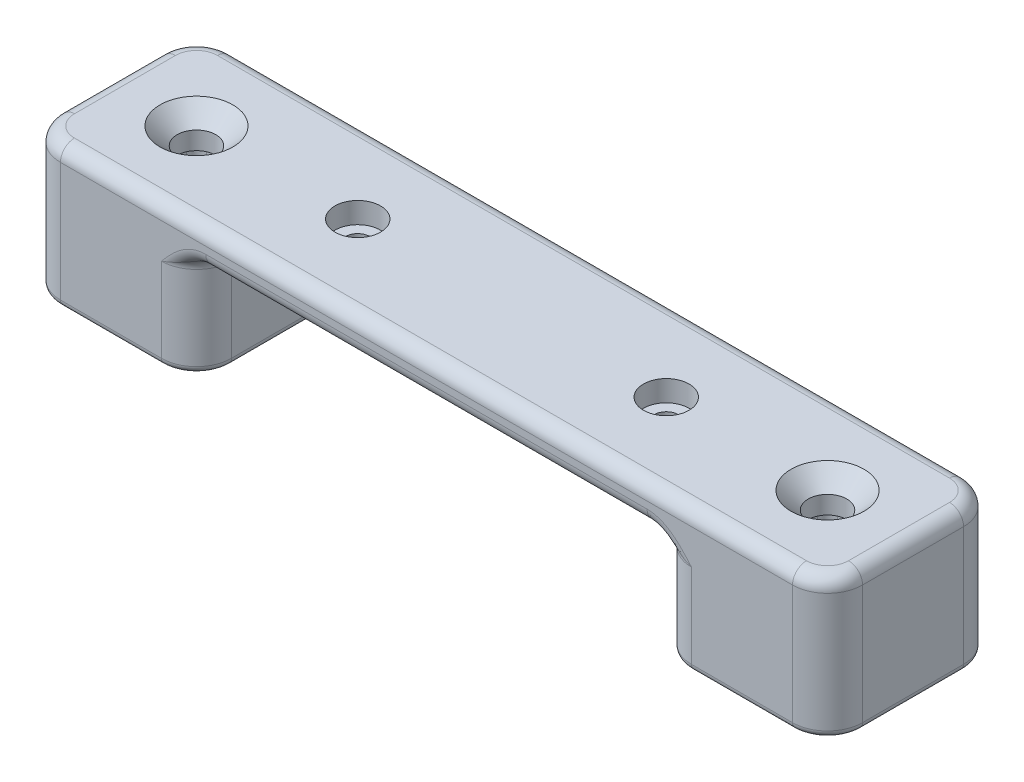
SolidWorks part; units mm, degrees
ref_plane "Plan de face" through (0, 0, 0) normal (0, 0, 1) x (1, 0, 0)
ref_plane "Plan de dessus" through (0, 0, 0) normal (0, 1, 0) x (1, 0, 0)
ref_plane "Plan de droite" through (0, 0, 0) normal (1, 0, 0) x (0, 0, -1)
sketch "Esquisse1" plane through (0, 0, 0) normal (0, 1, 0) x (1, 0, 0)
  line L0 (0, -55) -> (0, 55) construction
  line L1 (-57.2, 12.2) -> (57.2, 12.2)
  line L2 (-57.2, 12.2) -> (-57.2, -12.2)
  line L3 (-57.2, -12.2) -> (57.2, -12.2)
  line L4 (57.2, 12.2) -> (57.2, -12.2)
  line L5 (-55, 0) -> (55, 0) construction
  point P6 (0, -12.2)
  point P11 (57.2, 0)
  dimension "D1" = 114.4
  dimension "D2" = 24.4
extrude "Boss.-Extru.1" add sketch "Esquisse1" along normal blind 5
sketch "Esquisse11" plane through (0, 0, 0) normal (0, -1, 0) x (1, 0, 0)
  line L0 (57.2, -12.2) -> (-57.2, -12.2) construction
  line L1 (-57.2, 12.2) -> (-32.8, 12.2)
  line L2 (-57.2, 12.2) -> (-57.2, -12.2)
  line L3 (-57.2, -12.2) -> (-32.8, -12.2)
  line L4 (-32.8, 12.2) -> (-32.8, -12.2)
  line L10 (57.2, 12.2) -> (32.8, 12.2)
  line L11 (57.2, 12.2) -> (57.2, -12.2)
  line L12 (57.2, -12.2) -> (32.8, -12.2)
  line L13 (32.8, 12.2) -> (32.8, -12.2)
extrude "Boss.-Extru.2" add sketch "Esquisse11" along normal blind 15
sketch "Esquisse12" plane through (0, -15, 0) normal (0, -1, 0) x (1, 0, 0)
  line L8 (-34.8, -10.2) -> (-34.8, 10.2)
  line L9 (-55.2, -10.2) -> (-34.8, -10.2)
  line L10 (-55.2, 10.2) -> (-55.2, -10.2)
  line L11 (-34.8, 10.2) -> (-55.2, 10.2)
  line L12 (-34.8, -10.2) -> (-34.8, 10.2)
  line L13 (-55.2, -10.2) -> (-34.8, -10.2)
  line L14 (-55.2, 10.2) -> (-55.2, -10.2)
  line L15 (-34.8, 10.2) -> (-55.2, 10.2)
  line L20 (55.2, -10.2) -> (55.2, 10.2)
  line L21 (34.8, -10.2) -> (55.2, -10.2)
  line L22 (34.8, 10.2) -> (34.8, -10.2)
  line L23 (55.2, 10.2) -> (34.8, 10.2)
  line L24 (55.2, -10.2) -> (55.2, 10.2)
  line L25 (34.8, -10.2) -> (55.2, -10.2)
  line L26 (34.8, 10.2) -> (34.8, -10.2)
  line L27 (55.2, 10.2) -> (34.8, 10.2)
  dimension "D1" = 2
  dimension "D2" = 2
extrude "Enlèv. mat.-Extru.5" cut sketch "Esquisse12" against normal up to surface (15 mm away) up to face at (0, 0, 0)
sketch "Esquisse20" plane through (0, 5, 0) normal (0, 1, 0) x (1, 0, 0)
  line L0 (-45, 0) -> (45, 0) construction
  point P2 (-45, 0)
  dimension "D1" = 90
hole_wizard "Fraisage pour vis à tête fraisée M51" positions "Esquisse21" profile "Esquisse22" countersink size "M5" standard "ISO" end condition up to next
sketch "Esquisse21" plane through (0, 5, 0) normal (0, 1, 0) x (1, 0, 0)
  point P0 (-45, 0)
  point P3 (45, 0)
sketch "Esquisse22" plane through (-45, 5, 0) normal (1, 0, 0) x (0, 0, 1)
  line L0 (0, 0) -> (0, 5)
  line L1 (0, 5) -> (2.75, 5)
  line L2 (2.75, 5) -> (2.75, 2.45)
  line L3 (2.75, 2.45) -> (5.2, 0)
  line L5 (5.2, 0) -> (0, 0)
  line L6 (-2.75, 2.45) -> (-5.2, 0) construction
  line L11 (0, -6.35) -> (0, 107.95) construction
  dimension "Diamètre du perçage jusqu'au prochain" = 5.5
  dimension "Profondeur du perçage jusqu'au prochain" = 5
  dimension "Diamètre du fraisage entrant" = 10.4
  dimension "Angle du fraisage entrant" = 90
fillet "Congé4" radius 5 8 edges at (-57.2, -5, -12.2) (-32.8, -7.5, -12.2) (-32.8, -7.5, 12.2) (32.8, -7.5, 12.2) (32.8, -7.5, -12.2) (57.2, -5, -12.2) (57.2, -5, 12.2) (-57.2, -5, 12.2)
fillet "Congé6" radius 1 16 edges at (55.7355, -15, -10.7355) (45, -15, -12.2) (34.2645, -15, -10.7355) (32.8, -15, 0) (34.2645, -15, 10.7355) (45, -15, 12.2) (55.7355, -15, 10.7355) (-34.2645, -15, 10.7355) (-32.8, -15, 0) (-34.2645, -15, -10.7355) (-45, -15, -12.2) (-55.7355, -15, -10.7355) (-57.2, -15, 0) (-55.7355, -15, 10.7355) (57.2, -15, 0) (-45, -15, 12.2)
fillet "Congé7" radius 1.4 8 edges at (55.2, -7.4851, -10.2) (34.8, -7.4851, -10.2) (55.2, -7.4851, 10.2) (34.8, -7.4851, 10.2) (-55.2, -7.4851, -10.2) (-55.2, -7.4851, 10.2) (-34.8, -7.4851, -10.2) (-34.8, -7.4851, 10.2)
fillet "Congé8" radius 2 16 edges at (-55.7355, 5, 10.7355) (-57.2, 5, 0) (-55.7355, 5, -10.7355) (0, 5, -12.2) (55.7355, 5, -10.7355) (57.2, 5, 0) (55.7355, 5, 10.7355) (0, 5, 12.2) (0, 0, -12.2) (0, 0, 12.2) (34.2645, 0, 10.7355) (34.2645, 0, -10.7355) (-34.2645, 0, -10.7355) (-34.2645, 0, 10.7355) (32.8, 0, 0) (-32.8, 0, 0)
hole_wizard "Chambrage pour vis à tête hexagonale M31" positions "Esquisse23" profile "Esquisse24" counterbore size "M3" standard "ISO"
sketch "Esquisse23" plane through (0, 5, 0) normal (0, 1, 0) x (1, 0, 0)
  line L0 (22, 0) -> (-22, 0) construction
  point P0 (-22, 0)
  point P2 (22, 0)
  point P62 (0, 0)
  point P63 (0, 0)
  point P65 (23.6729, 0)
  dimension "D1" = 44
sketch "Esquisse24" plane through (-22, 5, 0) normal (1, 0, 0) x (0, 0, 1)
  line L0 (0, 0) -> (0, 6.0215)
  line L1 (0, 6.0215) -> (1.7, 5)
  line L2 (1.7, 5) -> (1.7, 3)
  line L3 (1.7, 3) -> (3.25, 3)
  line L4 (3.25, 3) -> (3.25, 0)
  line L5 (3.25, 0) -> (0, 0)
  line L10 (0, 6.0215) -> (-1.7, 5) construction
  line L11 (0, -6.35) -> (0, 107.95) construction
  dimension "Diamètre du perçage" = 3.4
  dimension "Profondeur du perçage" = 5
  dimension "Diamètre du chambrage" = 6.5
  dimension "Profondeur du chambrage" = 3
  dimension "Angle de pointe" = 118
